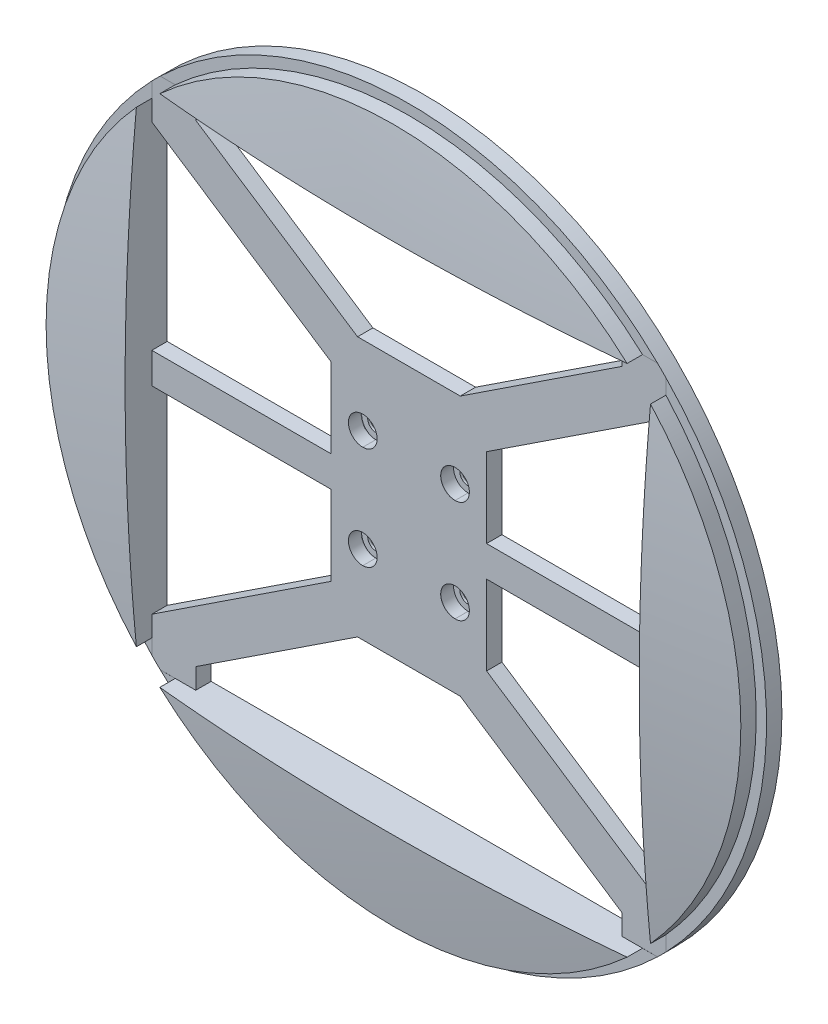
SolidWorks part; units mm, degrees
ref_plane "Front Plane" through (0, 0, 0) normal (0, 0, 1) x (1, 0, 0)
ref_plane "Top Plane" through (0, 0, 0) normal (0, 1, 0) x (1, 0, 0)
ref_plane "Right Plane" through (0, 0, 0) normal (1, 0, 0) x (0, 0, -1)
sketch "Sketch1" plane through (0, 0, 0) normal (0, 0, 1) x (1, 0, 0)
  line L0 (-93.4588, 0) -> (6.5412, 0) construction
  line L1 (-93.4588, 50) -> (6.5412, 50)
  line L2 (-93.4588, 50) -> (-93.4588, -50)
  line L3 (-93.4588, -50) -> (6.5412, -50)
  line L4 (6.5412, 50) -> (6.5412, -50)
  line L5 (-43.4588, 50) -> (-43.4588, -50) construction
  line L6 (-49.4988, 72.2316) -> (-37.4187, 72.2316)
  line L7 (-26.8824, 70.5628) -> (-15.3936, 66.8299)
  line L8 (-5.8886, 61.9869) -> (3.8844, 54.8864)
  line L9 (11.4276, 47.3432) -> (18.5281, 37.5702)
  line L10 (23.3711, 28.0652) -> (27.104, 16.5764)
  line L11 (28.7728, 6.04) -> (28.7728, -6.04)
  line L12 (27.104, -16.5764) -> (23.3711, -28.0652)
  line L13 (18.5281, -37.5702) -> (11.4276, -47.3432)
  line L14 (3.8844, -54.8864) -> (-5.8886, -61.9869)
  line L15 (-15.3936, -66.8299) -> (-26.8824, -70.5628)
  line L16 (-37.4187, -72.2316) -> (-49.4988, -72.2316)
  line L17 (-60.0352, -70.5628) -> (-71.524, -66.8299)
  line L18 (-81.029, -61.9869) -> (-90.802, -54.8864)
  line L19 (-98.3451, -47.3432) -> (-105.4456, -37.5702)
  line L20 (-110.2887, -28.0652) -> (-114.0216, -16.5764)
  line L21 (-115.6904, -6.04) -> (-115.6904, 6.04)
  line L22 (-114.0216, 16.5764) -> (-110.2887, 28.0652)
  line L23 (-105.4456, 37.5702) -> (-98.3451, 47.3432)
  line L24 (-90.802, 54.8864) -> (-81.029, 61.9869)
  line L25 (-71.524, 66.8299) -> (-60.0352, 70.5628)
  circle A0 centre (-43.4588, 0) radius 85.2829 construction
  spline S0 degree 2 poles (-49.4988, 72.2316) (-53.4923, 75.188) (-55.848, 78.2222) knots 0 0 0 0.180444 0.180444 0.180444
  spline S1 degree 2 poles (-37.4187, 72.2316) (-33.4252, 75.188) (-31.0696, 78.2222) knots 0 0 0 0.180444 0.180444 0.180444
  spline S2 degree 2 poles (-15.3936, 66.8299) (10.7176, 75.5727) (-10.2733, 102.1343) knots 0 0 0 1 1 1
  spline S3 degree 2 poles (-26.8824, 70.5628) (-42.8679, 92.9837) (-10.2733, 102.1343) knots 0 0 0 1 1 1
  spline S4 degree 2 poles (3.8844, 54.8864) (8.8529, 54.9308) (12.5421, 56.0009) knots 0 0 0 0.180444 0.180444 0.180444
  spline S5 degree 2 poles (-5.8886, 61.9869) (-7.3817, 66.7259) (-7.504, 70.5652) knots 0 0 0 0.180444 0.180444 0.180444
  spline S6 degree 2 poles (18.5281, 37.5702) (44.7914, 29.2955) (43.4219, 63.1225) knots 0 0 0 1 1 1
  spline S7 degree 2 poles (11.4276, 47.3432) (11.6737, 74.8781) (43.4219, 63.1225) knots 0 0 0 1 1 1
  spline S8 degree 2 poles (27.104, 16.5764) (31.1497, 13.6919) (34.7634, 12.3892) knots 0 0 0 0.180444 0.180444 0.180444
  spline S9 degree 2 poles (23.3711, 28.0652) (24.9487, 32.7768) (27.1064, 35.9548) knots 0 0 0 0.180444 0.180444 0.180444
  spline S10 degree 2 poles (28.7728, -6.04) (45.1565, -28.1716) (63.9316, 0) knots 0 0 0 1 1 1
  spline S11 degree 2 poles (28.7728, 6.04) (45.1565, 28.1716) (63.9316, 0) knots 0 0 0 1 1 1
  spline S12 degree 2 poles (23.3711, -28.0652) (24.9487, -32.7768) (27.1064, -35.9548) knots 0 0 0 0.180444 0.180444 0.180444
  spline S13 degree 2 poles (27.104, -16.5764) (31.1497, -13.6919) (34.7634, -12.3892) knots 0 0 0 0.180444 0.180444 0.180444
  spline S14 degree 2 poles (11.4276, -47.3432) (11.6737, -74.8781) (43.4219, -63.1225) knots 0 0 0 1 1 1
  spline S15 degree 2 poles (18.5281, -37.5702) (44.7914, -29.2955) (43.4219, -63.1225) knots 0 0 0 1 1 1
  spline S16 degree 2 poles (-5.8886, -61.9869) (-7.3817, -66.7259) (-7.504, -70.5652) knots 0 0 0 0.180444 0.180444 0.180444
  spline S17 degree 2 poles (3.8844, -54.8864) (8.8529, -54.9308) (12.5421, -56.0009) knots 0 0 0 0.180444 0.180444 0.180444
  spline S18 degree 2 poles (-26.8824, -70.5628) (-42.8679, -92.9837) (-10.2733, -102.1343) knots 0 0 0 1 1 1
  spline S19 degree 2 poles (-15.3936, -66.8299) (10.7176, -75.5727) (-10.2733, -102.1343) knots 0 0 0 1 1 1
  spline S20 degree 2 poles (-49.4988, -72.2316) (-71.6304, -88.6153) (-43.4588, -107.3904) knots 0 0 0 1 1 1
  spline S21 degree 2 poles (-37.4187, -72.2316) (-33.4252, -75.188) (-31.0696, -78.2222) knots 0 0 0 0.180444 0.180444 0.180444
  spline S22 degree 2 poles (-71.524, -66.8299) (-97.6352, -75.5727) (-76.6442, -102.1343) knots 0 0 0 1 1 1
  spline S23 degree 2 poles (-60.0352, -70.5628) (-44.0496, -92.9837) (-76.6442, -102.1343) knots 0 0 0 1 1 1
  spline S24 degree 2 poles (-90.802, -54.8864) (-95.7705, -54.9308) (-99.4597, -56.0009) knots 0 0 0 0.180444 0.180444 0.180444
  spline S25 degree 2 poles (-81.029, -61.9869) (-79.5359, -66.7259) (-79.4136, -70.5652) knots 0 0 0 0.180444 0.180444 0.180444
  spline S26 degree 2 poles (-105.4456, -37.5702) (-131.7089, -29.2955) (-130.3394, -63.1225) knots 0 0 0 1 1 1
  spline S27 degree 2 poles (-98.3451, -47.3432) (-98.5912, -74.8781) (-130.3394, -63.1225) knots 0 0 0 1 1 1
  spline S28 degree 2 poles (-114.0216, -16.5764) (-118.0673, -13.6919) (-121.6809, -12.3892) knots 0 0 0 0.180444 0.180444 0.180444
  spline S29 degree 2 poles (-110.2887, -28.0652) (-111.8662, -32.7768) (-114.024, -35.9548) knots 0 0 0 0.180444 0.180444 0.180444
  spline S30 degree 2 poles (-115.6904, 6.04) (-132.0741, 28.1716) (-150.8492, 0) knots 0 0 0 1 1 1
  spline S31 degree 2 poles (-115.6904, -6.04) (-132.0741, -28.1716) (-150.8492, 0) knots 0 0 0 1 1 1
  spline S32 degree 2 poles (-110.2887, 28.0652) (-111.8662, 32.7768) (-114.024, 35.9548) knots 0 0 0 0.180444 0.180444 0.180444
  spline S33 degree 2 poles (-114.0216, 16.5764) (-118.0673, 13.6919) (-121.6809, 12.3892) knots 0 0 0 0.180444 0.180444 0.180444
  spline S34 degree 2 poles (-98.3451, 47.3432) (-98.5912, 74.8781) (-130.3394, 63.1225) knots 0 0 0 1 1 1
  spline S35 degree 2 poles (-105.4456, 37.5702) (-131.7089, 29.2955) (-130.3394, 63.1225) knots 0 0 0 1 1 1
  spline S36 degree 2 poles (-81.029, 61.9869) (-79.5359, 66.7259) (-79.4136, 70.5652) knots 0 0 0 0.180444 0.180444 0.180444
  spline S37 degree 2 poles (-90.802, 54.8864) (-95.7705, 54.9308) (-99.4597, 56.0009) knots 0 0 0 0.180444 0.180444 0.180444
  spline S38 degree 2 poles (-60.0352, 70.5628) (-44.0496, 92.9837) (-76.6442, 102.1343) knots 0 0 0 1 1 1
  spline S39 degree 2 poles (-71.524, 66.8299) (-97.6352, 75.5727) (-76.6442, 102.1343) knots 0 0 0 1 1 1
  spline S40 degree 2 poles (-58.0959, 92.4149) (-54.9948, 99.7021) (-43.4588, 107.3904) knots 0.590507 0.590507 0.590507 1 1 1
  spline S41 degree 2 poles (-28.8217, 92.4149) (-31.9227, 99.7021) (-43.4588, 107.3904) knots 0.590507 0.590507 0.590507 1 1 1
  spline S42 degree 2 poles (-0.9803, 83.3687) (5.8118, 87.4415) (19.6637, 86.8807) knots 0.590507 0.590507 0.590507 1 1 1
  spline S43 degree 2 poles (22.703, 66.1617) (24.4775, 73.88) (19.6637, 86.8807) knots 0.590507 0.590507 0.590507 1 1 1
  spline S44 degree 2 poles (39.9099, 42.4785) (47.7987, 41.7811) (58.6756, 33.1855) knots 0.590507 0.590507 0.590507 1 1 1
  spline S45 degree 2 poles (48.9561, -14.6371) (54.9284, -19.8382) (58.6756, -33.1855) knots 0.590507 0.590507 0.590507 1 1 1
  spline S46 degree 2 poles (48.9561, 14.6371) (54.9284, 19.8382) (58.6756, 33.1855) knots 0.590507 0.590507 0.590507 1 1 1
  spline S47 degree 2 poles (22.703, -66.1617) (24.4775, -73.88) (19.6637, -86.8807) knots 0.590507 0.590507 0.590507 1 1 1
  spline S48 degree 2 poles (39.9099, -42.4785) (47.7987, -41.7811) (58.6756, -33.1855) knots 0.590507 0.590507 0.590507 1 1 1
  spline S49 degree 2 poles (-28.8217, -92.4149) (-31.9227, -99.7021) (-43.4588, -107.3904) knots 0.590507 0.590507 0.590507 1 1 1
  spline S50 degree 2 poles (-0.9803, -83.3687) (5.8118, -87.4415) (19.6637, -86.8807) knots 0.590507 0.590507 0.590507 1 1 1
  spline S51 degree 2 poles (-85.9372, -83.3687) (-92.7294, -87.4415) (-106.5813, -86.8807) knots 0.590507 0.590507 0.590507 1 1 1
  spline S52 degree 2 poles (-109.6205, -66.1617) (-111.3951, -73.88) (-106.5813, -86.8807) knots 0.590507 0.590507 0.590507 1 1 1
  spline S53 degree 2 poles (-126.8274, -42.4785) (-134.7163, -41.7811) (-145.5931, -33.1855) knots 0.590507 0.590507 0.590507 1 1 1
  spline S54 degree 2 poles (-135.8737, -14.6371) (-141.846, -19.8382) (-145.5931, -33.1855) knots 0.590507 0.590507 0.590507 1 1 1
  spline S55 degree 2 poles (-135.8737, 14.6371) (-141.846, 19.8382) (-145.5931, 33.1855) knots 0.590507 0.590507 0.590507 1 1 1
  spline S56 degree 2 poles (-109.6205, 66.1617) (-111.3951, 73.88) (-106.5813, 86.8807) knots 0.590507 0.590507 0.590507 1 1 1
  spline S57 degree 2 poles (-126.8274, 42.4785) (-134.7163, 41.7811) (-145.5931, 33.1855) knots 0.590507 0.590507 0.590507 1 1 1
  spline S58 degree 2 poles (-85.9372, 83.3687) (-92.7294, 87.4415) (-106.5813, 86.8807) knots 0.590507 0.590507 0.590507 1 1 1
  point P11 (-43.4588, 0)
  point P115 (-43.4588, 0)
  dimension "D1" = 100
  dimension "D2" = 100
  dimension "D3" = 20
extrude "Boss-Extrude1" add sketch "Sketch1" along normal blind 3 contours L25 S39 S36 L24 S37 S34 L23 S35 S32 L22 S33 S30 L21 S31 S28 L20 S29 S26 L19 S27 S24 L18 S25 S22 L17 S23 S20 L16 S21 S18 L15 S19 S16 L14 S17 S14 L13 S15 S12 L12 S13 S10 L11 S11 S8 L10 S9 S6 L9 S7 S4 | L4 L1 L2 L3 | S15 S48 S45 S10 S13 L12 S12 | S11 L11 S10 | S11 S46 S44 S6 S9 L10 S8 | S7 L9 S6 | S7 S43 S42 S2 S5 L8 S4 | S3 L7 S2 | S3 S41 S40 S38 S0 L6 S1 | S39 L25 S38 | S39 S58 S56 S34 S37 L24 S36 | S35 L23 S34 | S35 S57 S55 S30 S33 L22 S32 | S31 L21 S30 | S31 S54 S53 S26 S29 L20 S28 | S27 L19 S26 | S27 S52 S51 S22 S25 L18 S24 | S23 L17 S22 S20 | S49 S18 S21 L16 S20 S23 | S19 L15 S18 | S19 S50 S47 S14 S17 L14 S16 | S15 L13 S14 | S23 S20 region at (-43.4588, 0, 0) region at (-43.4588, 88.3743, 0) region at (-43.4588, 70.0192, 0) region at (-70.6753, 83.7637, 0) region at (-16.2423, 83.7637, 0) region at (-95.4039, 71.4963, 0) region at (8.4863, 71.4963, 0) region at (-114.7125, 51.7688, 0) region at (27.7949, 51.7688, 0) region at (-127.5077, 27.3092, 0) region at (40.5902, 27.3092, 0) region at (-131.5332, 0, 0) region at (44.6156, 0, 0) region at (-127.5077, -27.3092, 0) region at (40.5902, -27.3092, 0) region at (-114.7125, -51.7688, 0) region at (27.7949, -51.7688, 0) region at (-95.4039, -71.4963, 0) region at (8.4863, -71.4963, 0) region at (-71.4046, -83.676, 0) region at (-16.2423, -83.7637, 0) region at (-43.4588, -88.3743, 0) region at (-56.9864, -85.41, 0)
extrude "Boss-Extrude2" add sketch "Sketch1<3>" along normal blind 6 contours L25 S39 S36 L24 S37 S34 L23 S35 S32 L22 S33 S30 L21 S31 S28 L20 S29 S26 L19 S27 S24 L18 S25 S22 L17 S23 S20 L16 S21 S18 L15 S19 S16 L14 S17 S14 L13 S15 S12 L12 S13 S10 L11 S11 S8 L10 S9 S6 L9 S7 S4 | S3 L7 S2 | S7 L9 S6 | S11 L11 S10 | S15 L13 S14 | S19 L15 S18 | S23 L17 S22 S20 | S23 S20 | S27 L19 S26 | S31 L21 S30 | S35 L23 S34 | S39 L25 S38 region at (-43.4588, 70.0192, 0) region at (-70.6753, 83.7637, 0) region at (-16.2423, 83.7637, 0) region at (-114.7125, 51.7688, 0) region at (27.7949, 51.7688, 0) region at (-131.5332, 0, 0) region at (44.6156, 0, 0) region at (-114.7125, -51.7688, 0) region at (27.7949, -51.7688, 0) region at (-71.4046, -83.676, 0) region at (-16.2423, -83.7637, 0) region at (-56.9864, -85.41, 0)
sketch "Sketch1<3>" plane through (0, 0, 0) normal (0, 0, 1) x (1, 0, 0) same geometry as "Sketch1"
ref_plane "Plane1" through (-43.4588, 0, 0) normal (1, 0, 0) x (0, 0, -1)
sketch "Sketch2" plane through (-43.4588, 0, 0) normal (1, 0, 0) x (0, 0, -1)
  line L0 (-3, 0) -> (-11, 0)
  line L1 (-6, 0) -> (0, 0) construction
  line L2 (-3, 0) -> (-3, 72.0897)
  line L3 (-3, 72.0897) -> (-5.3749, 72.0897)
  spline S0 degree 2 poles (-5.3749, 72.0897) (-10.8416, 36.0521) (-11, 0) knots 0 0 0 0.499655 0.499655 0.499655
revolve "Revolve1" add sketch "Sketch2" angle 360 about L0
sketch "Sketch3" plane through (0, 0, 6) normal (0, 0, 1) x (1, 0, 0)
  line L0 (6.6912, 0) -> (-93.6088, 0) construction
  line L1 (-93.6088, -50.15) -> (6.6912, -50.15)
  line L2 (-93.6088, -50.15) -> (-93.6088, 50.15)
  line L3 (-93.6088, 50.15) -> (6.6912, 50.15)
  line L4 (6.6912, -50.15) -> (6.6912, 50.15)
  line L5 (-43.4588, -50.15) -> (-43.4588, 50.15) construction
  arc A1 (-93.4588, 45.862) -> (-93.4588, -45.862) centre (-43.4588, 0) ccw construction
  point P16 (-43.4588, 0)
  dimension "D1" = 100.3
extrude "Cut-Extrude1" cut sketch "Sketch3" along normal blind 29 and the other way blind 3
sketch "Sketch4" plane through (-43.4588, 0, 0) normal (1, 0, 0) x (0, 0, -1)
  line L0 (-6.0111, 67.77) -> (-3.0111, 67.77)
  line L1 (-3.0111, 67.77) -> (-3, 69.7699)
  line L2 (-3, 86.8807) -> (-3, 66.1617) construction
  line L3 (-3, 69.7699) -> (3, 69.7699)
  line L4 (3, 69.7699) -> (3, 70.0699)
  line L5 (3, 70.0699) -> (-3.3, 70.0699)
  line L6 (-3.3, 70.0699) -> (-3.3, 68.0699)
  line L7 (-3.3, 68.0699) -> (-6.632, 68.0699)
  line L8 (-6.632, 68.0699) -> (-6.632, 67.77)
  line L9 (-6.632, 67.77) -> (-6.0111, 67.77)
  line L10 (0, 0) -> (-25.3635, 0) construction
  spline S0 degree 3 poles (-6, 67.8477) (-6.0167, 67.7306) (-6.0631, 67.4056) (-6.1386, 66.8727) (-6.2846, 65.8332) (-6.5981, 63.5583) (-7.1408, 59.4314) (-7.5895, 55.716) (-7.8953, 53.0284) (-7.9886, 52.1948) (-8.0802, 51.3611) (-8.1468, 50.749) (-8.1901, 50.3453) (-8.211, 50.15) knots 0 0 0 0 0.019893 0.055215 0.090531 0.196442 0.441477 0.790622 0.8259 0.896442 0.931705 0.966964 1 1 1 1 construction
  dimension "D1" = 3
revolve "Cut-Revolve1" cut sketch "Sketch4" angle 360 about L10
delete or keep bodies "Body-Delete/Keep 1" type delete bodies bodies 105
sketch "Sketch5" plane through (0, 0, 3) normal (0, 0, 1) x (1, 0, 0)
  line L0 (-93.6088, 45.5823) -> (-93.6088, 41.5823) construction
  line L1 (-93.6088, -45.5823) -> (-93.6088, 45.5823) construction
  line L2 (-93.6088, -45.5823) -> (-93.6088, -41.5823) construction
  line L3 (-93.6088, -41.5823) -> (-93.6088, 41.5823) construction
  line L4 (-93.6088, 0) -> (-58.6088, 0) construction
  line L5 (-93.6088, 41.5823) -> (-58.6088, 18.5264)
  line L6 (-58.6088, 18.5264) -> (-58.6088, 0) construction
  line L7 (-58.6088, 0) -> (-93.6088, 0) construction
  line L8 (-93.6088, 41.5823) -> (-93.6088, 0) construction
  line L9 (-93.6088, 3) -> (-58.6088, 3)
  line L10 (-93.6088, 41.5823) -> (-93.6088, 3)
  line L11 (-58.6088, 18.5264) -> (-58.6088, 3)
  line L12 (-93.6088, -41.5823) -> (-58.6088, -18.5264)
  line L13 (-93.6088, -41.5823) -> (-93.6088, -3)
  line L14 (-93.6088, -3) -> (-58.6088, -3)
  line L15 (-58.6088, -18.5264) -> (-58.6088, -3)
  line L16 (-43.4588, -50.15) -> (-43.4588, 50.15) construction
  line L17 (2.1235, -50.15) -> (-89.0411, -50.15) construction
  line L18 (-89.0411, 50.15) -> (2.1235, 50.15) construction
  line L19 (6.6912, 41.5823) -> (-28.3088, 18.5264)
  line L20 (6.6912, 41.5823) -> (6.6912, 3)
  line L21 (6.6912, 3) -> (-28.3088, 3)
  line L22 (-28.3088, 18.5264) -> (-28.3088, 3)
  line L23 (6.6912, -41.5823) -> (6.6912, -3)
  line L24 (6.6912, -3) -> (-28.3088, -3)
  line L25 (-28.3088, -18.5264) -> (-28.3088, -3)
  line L26 (6.6912, -41.5823) -> (-28.3088, -18.5264)
  line L27 (-89.0411, 50.15) -> (-85.0411, 50.15) construction
  line L28 (2.1235, 50.15) -> (-1.8765, 50.15) construction
  line L29 (-85.0411, 50.15) -> (-1.8765, 50.15)
  line L30 (-1.8765, 50.15) -> (-1.8765, 46.15)
  line L31 (-85.0411, 50.15) -> (-85.0411, 46.15)
  line L32 (-85.0411, 46.15) -> (-53.4757, 25.3566)
  line L33 (-1.8765, 46.15) -> (-33.4419, 25.3566)
  line L34 (-53.4757, 25.3566) -> (-33.4419, 25.3566)
  line L35 (-85.0411, -46.15) -> (-53.4757, -25.3566)
  line L36 (-85.0411, -50.15) -> (-85.0411, -46.15)
  line L37 (-85.0411, -50.15) -> (-1.8765, -50.15)
  line L38 (-1.8765, -50.15) -> (-1.8765, -46.15)
  line L39 (-1.8765, -46.15) -> (-33.4419, -25.3566)
  line L40 (-53.4757, -25.3566) -> (-33.4419, -25.3566)
  dimension "D1" = 35
  dimension "D2" = 3
extrude "Cut-Extrude2" cut sketch "Sketch5" against normal blind 31.5
sketch "Sketch6" plane through (0, 0, 3) normal (0, 0, 1) x (1, 0, 0)
  line L0 (-58.6088, 3) -> (-58.6088, -3) construction
  line L1 (-43.4588, 0) -> (-43.4588, 15) construction
  line L2 (-28.3088, -3) -> (-28.3088, 3) construction
  line L3 (-58.6088, 0) -> (-28.3088, 0) construction
  line L4 (-43.4588, 15) -> (-43.4588, -10) construction
  line L5 (-43.4588, -10) -> (-52.4588, -10) construction
  circle A0 centre (-52.4588, -10) radius 1.6
  dimension "D1" = 15
  dimension "D2" = 25
  dimension "D3" = 9
extrude "Cut-Extrude3" cut sketch "Sketch6" against normal blind 31.5
sketch "Sketch7" plane through (0, 0, 3) normal (0, 0, 1) x (1, 0, 0)
  circle A0 centre (-52.4588, -10) radius 2.8
extrude "Cut-Extrude4" cut sketch "Sketch7" against normal blind 2.5
ref_plane "Plane2" through (-43.4672, 0, 0.1272) normal (1, 0, -0.0029) x (-0.0029, 0, -1)
ref_plane "Plane3" through (0, 0, 0) normal (0, 1, 0) x (1, 0, 0)
mirror "Mirror1" about plane through (-43.4672, 0, 0.1272) normal (1, 0, -0.0029) of "Cut-Extrude3", "Cut-Extrude4" second plane through (0, 0, 0) second plane normal (0, 1, 0)
sketch "Sketch8" plane through (0, 0, 3) normal (0, 0, 1) x (1, 0, 0)
  line L0 (-43.4588, 25.3566) -> (-43.4588, -25.3566) construction
  line L1 (-53.4757, 25.3566) -> (-33.4419, 25.3566) construction
  line L2 (-33.4419, -25.3566) -> (-53.4757, -25.3566) construction
ref_axis "Axis1" through (-43.4588, 25.3566, 3) along (0, -1, 0)
ref_axis "Axis2" through (-43.4588, -25.3566, 3) along (0, 0, -1)
ref_plane "Plane4" through (-43.4588, 0, 0) normal (-1, 0, 0) x (0, 0, 1)
mirror "Mirror2" about plane through (-43.4588, 0, 0) normal (-1, 0, 0) of "Mirror1"
